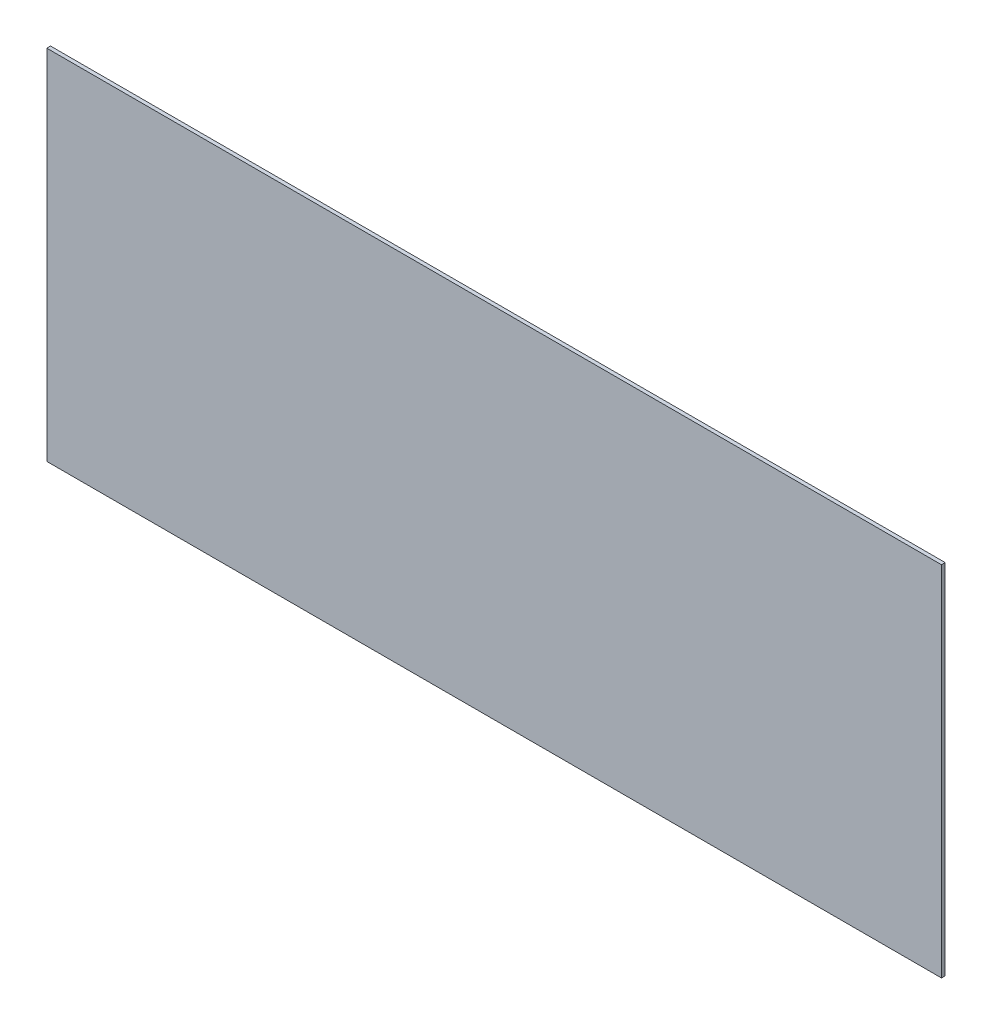
SolidWorks part; units mm, degrees
ref_plane "Front Plane" through (0, 0, 0) normal (0, 0, 1) x (1, 0, 0)
ref_plane "Top Plane" through (0, 0, 0) normal (0, 1, 0) x (1, 0, 0)
ref_plane "Right Plane" through (0, 0, 0) normal (1, 0, 0) x (0, 0, -1)
sketch "Sketch1" plane through (0, 0, 0) normal (0, 0, 1) x (1, 0, 0)
  line L1 (-238.8538, 271.0227) -> (523.1462, 271.0227)
  line L2 (-238.8538, 271.0227) -> (-238.8538, -33.7773)
  line L3 (-238.8538, -33.7773) -> (523.1462, -33.7773)
  line L4 (523.1462, 271.0227) -> (523.1462, -33.7773)
  dimension "D1" = 762
  dimension "D2" = 304.8
extrude "Boss-Extrude1" add sketch "Sketch1" along normal blind 3.175
